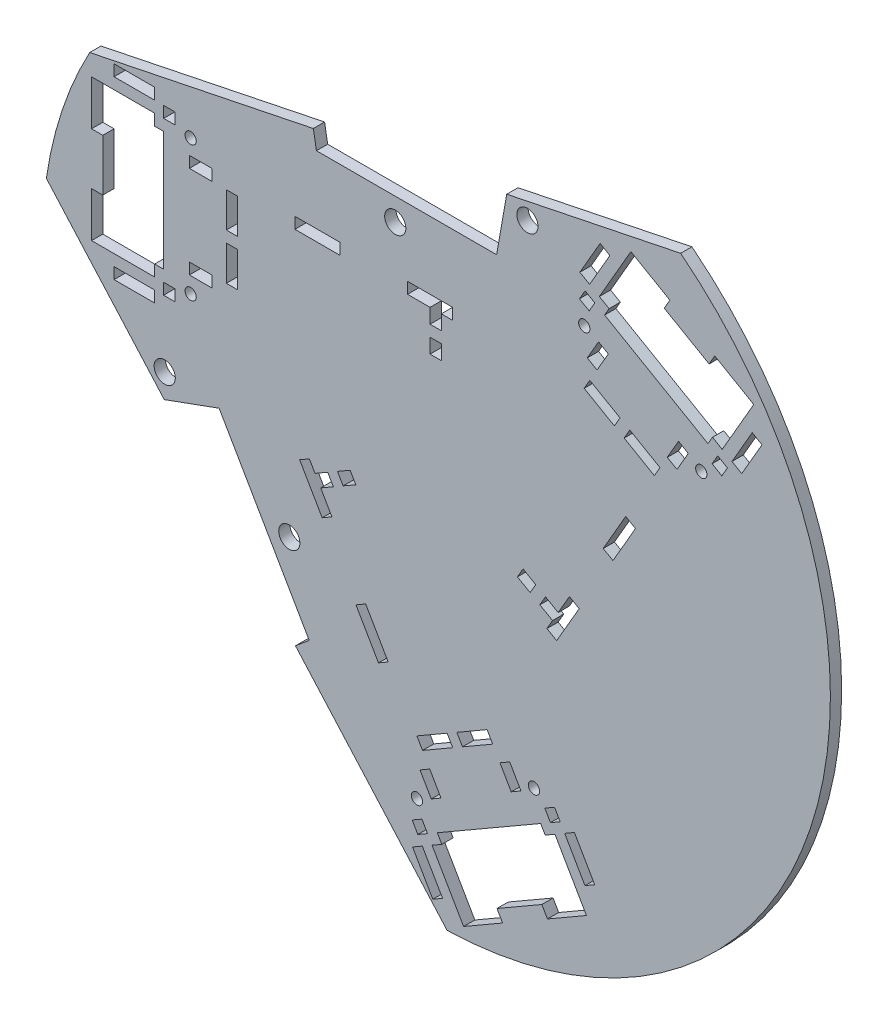
SolidWorks part; units mm, degrees
material "Balsa"
ref_plane "Plan de face" through (0, 0, 0) normal (0, 0, 1) x (1, 0, 0)
ref_plane "Plan de dessus" through (0, 0, 0) normal (0, 1, 0) x (1, 0, 0)
ref_plane "Plan de droite" through (0, 0, 0) normal (1, 0, 0) x (0, 0, -1)
sketch "Esquisse1" plane through (0, 0, 0) normal (0, 0, 1) x (1, 0, 0)
  circle A0 centre (148.0804, -12.1102) radius 175
extrude "Boss.-Extru.1" add sketch "Esquisse1" along normal blind 5
sketch "Esquisse2" plane through (0, 0, 0) normal (0, 0, -1) x (-1, 0, 0)
  line L0 (-155.3118, 53.7774) -> (-135.3118, 53.7774)
  line L1 (-150.3118, 37.2774) -> (-145.3118, 37.2774)
  line L2 (-150.3118, 37.2774) -> (-150.3118, 30.7774)
  line L3 (-150.3118, 30.7774) -> (-145.3118, 30.7774)
  line L4 (-145.3118, 37.2774) -> (-145.3118, 30.7774)
  line L5 (-105.3118, 53.7774) -> (-85.3118, 53.7774)
  line L6 (-105.3118, 53.7774) -> (-105.3118, 48.7774)
  line L7 (-105.3118, 48.7774) -> (-85.3118, 48.7774)
  line L8 (-85.3118, 53.7774) -> (-85.3118, 48.7774)
  line L9 (-59.86, 48.7774) -> (-54.86, 48.7774)
  line L10 (-59.86, 48.7774) -> (-59.86, 33.2774)
  line L11 (-59.86, 33.2774) -> (-54.86, 33.2774)
  line L12 (-54.86, 48.7774) -> (-54.86, 33.2774)
  line L13 (-59.86, 28.2774) -> (-54.86, 28.2774)
  line L14 (-59.86, 28.2774) -> (-59.86, 12.7774)
  line L15 (-59.86, 12.7774) -> (-54.86, 12.7774)
  line L16 (-54.86, 28.2774) -> (-54.86, 12.7774)
  line L17 (-48.43, 12.7774) -> (-38.43, 12.7774)
  line L18 (-48.43, 12.7774) -> (-48.43, 7.7774)
  line L19 (-48.43, 7.7774) -> (-38.43, 7.7774)
  line L20 (-38.43, 12.7774) -> (-38.43, 7.7774)
  line L21 (-32, -0.7226) -> (-27, -0.7226)
  line L22 (-32, -0.7226) -> (-32, -5.7226)
  line L23 (-32, -5.7226) -> (-27, -5.7226)
  line L24 (-27, -0.7226) -> (-27, -5.7226)
  line L25 (-23, -5.7226) -> (-5, -5.7226)
  line L26 (-23, -5.7226) -> (-23, -10.7226)
  line L27 (-23, -10.7226) -> (-5, -10.7226)
  line L28 (-5, -5.7226) -> (-5, -10.7226)
  line L29 (0, -0.7226) -> (5, -0.7226)
  line L30 (0, -0.7226) -> (0, 19.2774)
  line L31 (0, 19.2774) -> (5, 19.2774)
  line L32 (5, -0.7226) -> (5, 19.2774)
  line L33 (0, 42.2774) -> (5, 42.2774)
  line L34 (0, 42.2774) -> (0, 62.2774)
  line L35 (0, 62.2774) -> (5, 62.2774)
  line L36 (5, 42.2774) -> (5, 62.2774)
  line L37 (-23, 67.2774) -> (-5, 67.2774)
  line L38 (-23, 67.2774) -> (-23, 72.2774)
  line L39 (-23, 72.2774) -> (-5, 72.2774)
  line L40 (-5, 67.2774) -> (-5, 72.2774)
  line L41 (-27, 67.2774) -> (-32, 67.2774)
  line L42 (-27, 67.2774) -> (-27, 62.2774)
  line L43 (-27, 62.2774) -> (-32, 62.2774)
  line L44 (-32, 67.2774) -> (-32, 62.2774)
  line L45 (-38.43, 53.7774) -> (-48.43, 53.7774)
  line L46 (-38.43, 53.7774) -> (-38.43, 48.7774)
  line L47 (-38.43, 48.7774) -> (-48.43, 48.7774)
  line L48 (-48.43, 53.7774) -> (-48.43, 48.7774)
  line L49 (-135.3118, 53.7774) -> (-135.3118, 48.7774)
  line L50 (-135.3118, 48.7774) -> (-145.3118, 48.7774)
  line L51 (-135.3118, 48.7774) -> (-155.3118, 48.7774) construction
  line L52 (-145.3118, 48.7774) -> (-145.3118, 42.2774)
  line L53 (-145.3118, 42.2774) -> (-150.3118, 42.2774)
  line L54 (-150.3118, 42.2774) -> (-150.3118, 48.7774)
  line L55 (-150.3118, 48.7774) -> (-155.3118, 48.7774)
  line L56 (-155.3118, 48.7774) -> (-155.3118, 53.7774)
  line L57 (-87.4044, -38.7914) -> (-97.4044, -56.1119)
  line L58 (-104.1938, -34.8716) -> (-106.6938, -39.2017)
  line L59 (-104.1938, -34.8716) -> (-109.823, -31.6216)
  line L60 (-109.823, -31.6216) -> (-112.323, -35.9517)
  line L61 (-106.6938, -39.2017) -> (-112.323, -35.9517)
  line L62 (-112.4044, -82.0927) -> (-122.4044, -99.4132)
  line L63 (-112.4044, -82.0927) -> (-116.7345, -79.5927)
  line L64 (-116.7345, -79.5927) -> (-126.7345, -96.9132)
  line L65 (-122.4044, -99.4132) -> (-126.7345, -96.9132)
  line L66 (-139.4604, -118.9551) -> (-141.9604, -123.2852)
  line L67 (-139.4604, -118.9551) -> (-152.8838, -111.2051)
  line L68 (-152.8838, -111.2051) -> (-155.3838, -115.5352)
  line L69 (-141.9604, -123.2852) -> (-155.3838, -115.5352)
  line L70 (-157.2139, -108.7051) -> (-159.7139, -113.0352)
  line L71 (-157.2139, -108.7051) -> (-170.6373, -100.9551)
  line L72 (-170.6373, -100.9551) -> (-173.1373, -105.2852)
  line L73 (-159.7139, -113.0352) -> (-173.1373, -105.2852)
  line L74 (-176.3523, -110.8538) -> (-181.3523, -119.514)
  line L75 (-176.3523, -110.8538) -> (-180.6825, -108.3538)
  line L76 (-180.6825, -108.3538) -> (-185.6825, -117.014)
  line L77 (-181.3523, -119.514) -> (-185.6825, -117.014)
  line L78 (-196.2587, -118.3326) -> (-198.7587, -122.6627)
  line L79 (-196.2587, -118.3326) -> (-200.5888, -115.8326)
  line L80 (-200.5888, -115.8326) -> (-203.0888, -120.1627)
  line L81 (-198.7587, -122.6627) -> (-203.0888, -120.1627)
  line L82 (-205.0888, -123.6268) -> (-214.0888, -139.2153)
  line L83 (-205.0888, -123.6268) -> (-209.4189, -121.1268)
  line L84 (-209.4189, -121.1268) -> (-218.4189, -136.7153)
  line L85 (-214.0888, -139.2153) -> (-218.4189, -136.7153)
  line L86 (-212.2587, -146.0454) -> (-214.7587, -150.3755)
  line L87 (-212.2587, -146.0454) -> (-194.9382, -156.0454)
  line L88 (-194.9382, -156.0454) -> (-197.4382, -160.3755)
  line L89 (-214.7587, -150.3755) -> (-197.4382, -160.3755)
  line L90 (-175.0196, -167.5454) -> (-177.5196, -171.8755)
  line L91 (-175.0196, -167.5454) -> (-157.6991, -177.5454)
  line L92 (-157.6991, -177.5454) -> (-160.1991, -181.8755)
  line L93 (-177.5196, -171.8755) -> (-160.1991, -181.8755)
  line L94 (-141.869, -160.1268) -> (-150.869, -175.7153)
  line L95 (-141.869, -160.1268) -> (-137.5388, -162.6268)
  line L96 (-137.5388, -162.6268) -> (-146.5388, -178.2153)
  line L97 (-150.869, -175.7153) -> (-146.5388, -178.2153)
  line L98 (-139.869, -156.6627) -> (-137.369, -152.3326)
  line L99 (-139.869, -156.6627) -> (-144.1991, -154.1627)
  line L100 (-144.1991, -154.1627) -> (-141.6991, -149.8326)
  line L101 (-137.369, -152.3326) -> (-141.6991, -149.8326)
  line L102 (-145.8453, -140.014) -> (-140.8453, -131.3538)
  line L103 (-145.8453, -140.014) -> (-150.1754, -137.514)
  line L104 (-150.1754, -137.514) -> (-145.1754, -128.8538)
  line L105 (-140.8453, -131.3538) -> (-145.1754, -128.8538)
  line L106 (-97.4044, -56.1119) -> (-101.7345, -53.6119)
  line L107 (-101.7345, -53.6119) -> (-96.7345, -44.9517)
  line L108 (-96.7345, -44.9517) -> (-102.3637, -41.7017)
  line L109 (-102.3637, -41.7017) -> (-99.8637, -37.3716)
  line L110 (-99.8637, -37.3716) -> (-94.2345, -40.6216)
  line L111 (-94.2345, -40.6216) -> (-91.7345, -36.2914)
  line L112 (-91.7345, -36.2914) -> (-87.4044, -38.7914)
  line L113 (-201.5251, -51.3165) -> (-211.5251, -33.996)
  line L114 (-189.7357, -38.7364) -> (-192.2357, -34.4063)
  line L115 (-189.7357, -38.7364) -> (-184.1065, -35.4864)
  line L116 (-184.1065, -35.4864) -> (-186.6065, -31.1563)
  line L117 (-192.2357, -34.4063) -> (-186.6065, -31.1563)
  line L118 (-226.5251, -8.0153) -> (-236.5251, 9.3053)
  line L119 (-226.5251, -8.0153) -> (-222.195, -5.5153)
  line L120 (-222.195, -5.5153) -> (-232.195, 11.8053)
  line L121 (-236.5251, 9.3053) -> (-232.195, 11.8053)
  line L122 (-244.9209, 33.8472) -> (-247.4209, 38.1773)
  line L123 (-244.9209, 33.8472) -> (-231.4975, 41.5972)
  line L124 (-231.4975, 41.5972) -> (-233.9975, 45.9273)
  line L125 (-247.4209, 38.1773) -> (-233.9975, 45.9273)
  line L126 (-227.1673, 44.0972) -> (-229.6673, 48.4273)
  line L127 (-227.1673, 44.0972) -> (-213.7439, 51.8472)
  line L128 (-213.7439, 51.8472) -> (-216.2439, 56.1773)
  line L129 (-229.6673, 48.4273) -> (-216.2439, 56.1773)
  line L130 (-219.4589, 61.7458) -> (-224.4589, 70.4061)
  line L131 (-219.4589, 61.7458) -> (-215.1288, 64.2458)
  line L132 (-215.1288, 64.2458) -> (-220.1288, 72.9061)
  line L133 (-224.4589, 70.4061) -> (-220.1288, 72.9061)
  line L134 (-215.9826, 82.7246) -> (-218.4826, 87.0547)
  line L135 (-215.9826, 82.7246) -> (-211.6525, 85.2246)
  line L136 (-211.6525, 85.2246) -> (-214.1525, 89.5547)
  line L137 (-218.4826, 87.0547) -> (-214.1525, 89.5547)
  line L138 (-216.1525, 93.0188) -> (-225.1525, 108.6073)
  line L139 (-216.1525, 93.0188) -> (-211.8223, 95.5188)
  line L140 (-211.8223, 95.5188) -> (-220.8223, 111.1073)
  line L141 (-225.1525, 108.6073) -> (-220.8223, 111.1073)
  line L142 (-231.9826, 110.4374) -> (-234.4826, 114.7676)
  line L143 (-231.9826, 110.4374) -> (-249.3031, 100.4374)
  line L144 (-249.3031, 100.4374) -> (-251.8031, 104.7676)
  line L145 (-234.4826, 114.7676) -> (-251.8031, 104.7676)
  line L146 (-269.2217, 88.9374) -> (-271.7217, 93.2676)
  line L147 (-269.2217, 88.9374) -> (-286.5422, 78.9374)
  line L148 (-286.5422, 78.9374) -> (-289.0422, 83.2676)
  line L149 (-271.7217, 93.2676) -> (-289.0422, 83.2676)
  line L150 (-279.3723, 56.5188) -> (-288.3723, 72.1073)
  line L151 (-279.3723, 56.5188) -> (-283.7025, 54.0188)
  line L152 (-283.7025, 54.0188) -> (-292.7025, 69.6073)
  line L153 (-288.3723, 72.1073) -> (-292.7025, 69.6073)
  line L154 (-277.3723, 53.0547) -> (-274.8723, 48.7246)
  line L155 (-277.3723, 53.0547) -> (-273.0422, 55.5547)
  line L156 (-273.0422, 55.5547) -> (-270.5422, 51.2246)
  line L157 (-274.8723, 48.7246) -> (-270.5422, 51.2246)
  line L158 (-259.966, 49.9061) -> (-254.966, 41.2458)
  line L159 (-259.966, 49.9061) -> (-255.6359, 52.4061)
  line L160 (-255.6359, 52.4061) -> (-250.6359, 43.7458)
  line L161 (-254.966, 41.2458) -> (-250.6359, 43.7458)
  line L162 (-211.5251, -33.996) -> (-207.195, -31.496)
  line L163 (-207.195, -31.496) -> (-202.195, -40.1563)
  line L164 (-202.195, -40.1563) -> (-196.5658, -36.9063)
  line L165 (-196.5658, -36.9063) -> (-194.0658, -41.2364)
  line L166 (-194.0658, -41.2364) -> (-199.695, -44.4864)
  line L167 (-199.695, -44.4864) -> (-197.195, -48.8165)
  line L168 (-197.195, -48.8165) -> (-201.5251, -51.3165)
  point P204 (-148.0804, -12.1102)
  dimension "D1" = 3
extrude "Enlèv. mat.-Extru.1" cut sketch "Esquisse2" against normal blind 5
sketch "Esquisse3" plane through (0, 0, 0) normal (0, 0, -1) x (-1, 0, 0)
  line L0 (-59.86, 33.2774) -> (-59.86, 28.2774) construction
  line L1 (-59.86, 30.7774) -> (32.4397, 30.7774) construction
  line L2 (0, -0.7226) -> (-23, -0.7226)
  line L3 (-23, -0.7226) -> (-23, 4.2774)
  line L4 (-23, 4.2774) -> (-27, 4.2774)
  line L5 (-23, 57.2774) -> (-27, 57.2774)
  line L6 (-23, 62.2774) -> (-23, 57.2774)
  line L7 (0, 62.2774) -> (-23, 62.2774)
  line L8 (-27, 57.2774) -> (-27, 4.2774)
  line L9 (0, -0.7226) -> (0, 62.2774)
  line L10 (-212.2587, -146.0454) -> (-200.7587, -126.1268)
  line L11 (-200.7587, -126.1268) -> (-196.4286, -128.6268)
  line L12 (-196.4286, -128.6268) -> (-194.4286, -125.1627)
  line L13 (-150.5292, -155.1268) -> (-148.5292, -151.6627)
  line L14 (-146.1991, -157.6268) -> (-150.5292, -155.1268)
  line L15 (-157.6991, -177.5454) -> (-146.1991, -157.6268)
  line L16 (-148.5292, -151.6627) -> (-194.4286, -125.1627)
  line L17 (-212.2587, -146.0454) -> (-157.6991, -177.5454)
  line L18 (-152.8838, -111.2051) -> (-157.2139, -108.7051) construction
  line L19 (-155.0489, -109.9551) -> (-201.1987, -189.889) construction
  line L20 (-231.9826, 110.4374) -> (-220.4826, 90.5188)
  line L21 (-220.4826, 90.5188) -> (-224.8127, 88.0188)
  line L22 (-224.8127, 88.0188) -> (-222.8127, 84.5547)
  line L23 (-270.7121, 61.5188) -> (-268.7121, 58.0547)
  line L24 (-275.0422, 59.0188) -> (-270.7121, 61.5188)
  line L25 (-286.5422, 78.9374) -> (-275.0422, 59.0188)
  line L26 (-268.7121, 58.0547) -> (-222.8127, 84.5547)
  line L27 (-231.9826, 110.4374) -> (-286.5422, 78.9374)
  line L28 (-231.4975, 41.5972) -> (-227.1673, 44.0972) construction
  line L29 (-229.3324, 42.8472) -> (-275.4822, 122.781) construction
  point P42 (-148.0804, -12.1102)
  dimension "D1" = 5
  dimension "D2" = 4
  dimension "D3" = 23
  dimension "D4" = 3
extrude "Enlèv. mat.-Extru.2" cut sketch "Esquisse3" against normal blind 5
sketch "Esquisse4" plane through (0, 0, 0) normal (0, 0, -1) x (-1, 0, 0)
  line L0 (-32, 67.2774) -> (-32, 62.2774) construction
  line L1 (-38.43, 53.7774) -> (-48.43, 53.7774) construction
  line L2 (-27, 30.7774) -> (-93.5454, 30.7774) construction
  line L3 (-27, 57.2774) -> (-27, 4.2774) construction
  line L4 (-171.4789, -138.4127) -> (-138.2062, -80.7827) construction
  line L5 (-245.7624, 71.3047) -> (-212.4897, 13.6748) construction
  circle A0 centre (-39, 60.7774) radius 2.5
  circle A1 centre (-39, 0.7774) radius 2.5
  circle A2 centre (-139.4981, -143.0204) radius 2.5
  circle A3 centre (-191.4596, -113.0204) radius 2.5
  circle A4 centre (-265.7432, 45.9124) radius 2.5
  circle A5 centre (-213.7816, 75.9124) radius 2.5
  point P27 (-148.0804, -12.1102)
  dimension "D1" = 7
  dimension "D2" = 7
  dimension "D3" = 3
extrude "Enlèv. mat.-Extru.3" cut sketch "Esquisse4" against normal blind 5
sketch "Esquisse5" plane through (0, 0, 0) normal (0, 0, -1) x (-1, 0, 0)
  line L0 (9.5132, 70.4436) -> (-93.4749, 91.6327)
  line L1 (-315.6994, 137.3538) -> (-290.7872, 258.4377)
  line L2 (-290.7872, 258.4377) -> (34.4253, 191.5275)
  line L3 (34.4253, 191.5275) -> (9.5132, 70.4436)
  line L5 (-179.3609, 109.3031) -> (-315.6994, 137.3538)
  line L6 (-94.86, 83.7774) -> (-174.86, 83.7774)
  line L7 (-174.86, 83.7774) -> (-179.3609, 109.3031)
  line L9 (-93.4749, 91.6327) -> (-94.86, 83.7774)
  line L10 (-155.3836, -189.8671) -> (-85.5392, -111.2714)
  line L11 (65.1687, 58.3201) -> (157.5743, -23.7964)
  line L12 (26.9196, -12.1102) -> (-148.0804, -12.1102) construction
  line L13 (157.5743, -23.7964) -> (-62.978, -271.9836)
  line L14 (-62.978, -271.9836) -> (-155.3836, -189.8671)
  line L16 (-27.2932, -45.7272) -> (65.1687, 58.3201)
  line L17 (-91.6495, -106.1442) -> (-51.6495, -36.8622)
  line L18 (-51.6495, -36.8622) -> (-27.2932, -45.7272)
  line L20 (-85.5392, -111.2714) -> (-91.6495, -106.1442)
  line L21 (-148.0804, -12.1102) -> (-235.5804, -163.6646) construction
  line L22 (-93.4749, 91.6327) -> (-179.3609, 109.3031) construction
  line L23 (-139.86, 83.7774) -> (-139.86, 101.1761) construction
  circle A0 centre (-188.5408, 103.7774) radius 4.7
  circle A1 centre (-129.86, 73.7774) radius 4.7
  circle A2 centre (-27.4886, -35.0143) radius 4.7
  circle A3 centre (-82.8098, -70.8333) radius 4.7
  point P15 (-148.0804, -12.1102)
  point P35 (-148.0804, -12.1102)
  dimension "D2" = 9.4
  dimension "D3" = 9.4
  dimension "D4" = 100
  dimension "D5" = 100
  dimension "D7" = 45
  dimension "D9" = 80
  dimension "D10" = 35
  dimension "D11" = 85.8876
  dimension "D12" = 58.6808
  dimension "D13" = 30
  dimension "D14" = 10
  dimension "D15" = 11.626
  dimension "D16" = 18.2204
  dimension "D18" = 17.3986
  dimension "D17" = 2
extrude "Enlèv. mat.-Extru.4" cut sketch "Esquisse5" against normal blind 5
